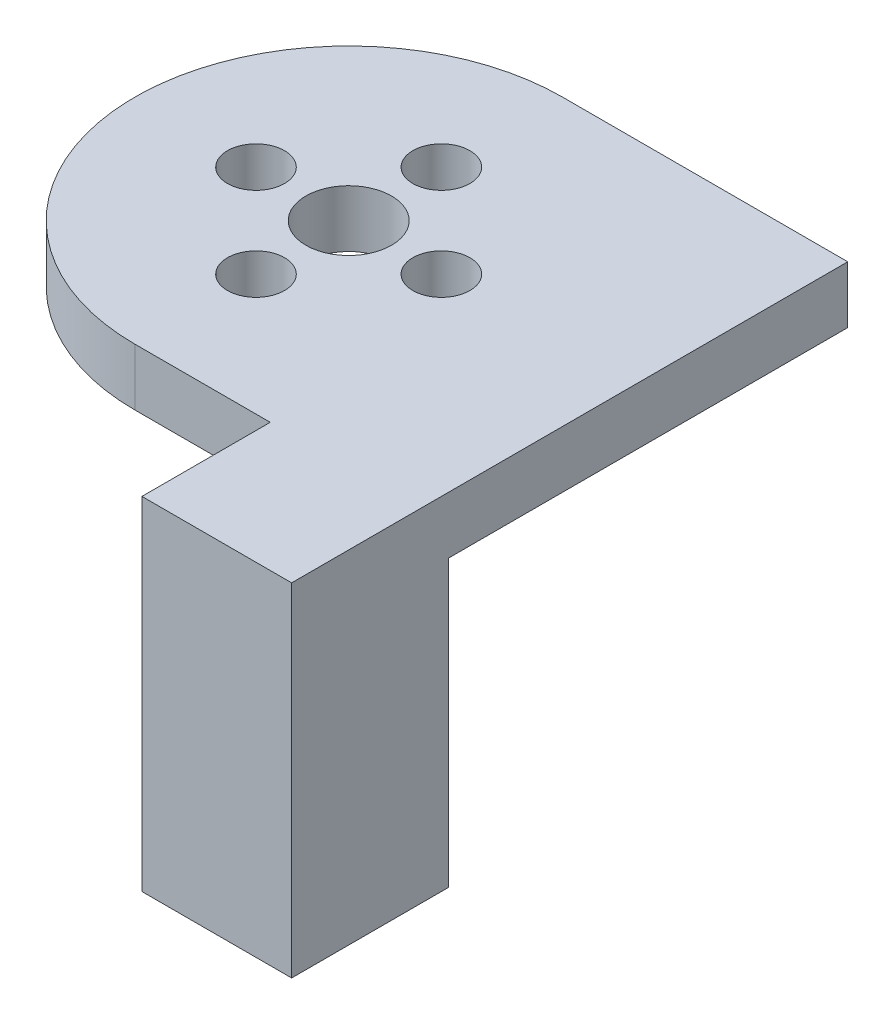
SolidWorks part; units mm, degrees
ref_plane "Front Plane" through (0, 0, 0) normal (0, 0, 1) x (1, 0, 0)
ref_plane "Top Plane" through (0, 0, 0) normal (0, 1, 0) x (1, 0, 0)
ref_plane "Right Plane" through (0, 0, 0) normal (1, 0, 0) x (0, 0, -1)
sketch "Sketch1" plane through (0, 0, 0) normal (0, 1, 0) x (1, 0, 0)
  line L1 (10, -15) -> (-10, -15)
  line L2 (10, -15) -> (10, 15)
  line L3 (10, 15) -> (-10, 15)
  line L5 (10, -15) -> (-10, 15) construction
  line L6 (10, 15) -> (-10, -15) construction
  arc A0 (-10, 15) -> (-10, -15) centre (-10, 0) ccw
  circle A1 centre (-10, 0) radius 3
  circle A2 centre (-10, 6.5) radius 2
  circle A3 centre (-3.5, 0) radius 2
  circle A4 centre (-10, -6.5) radius 2
  circle A5 centre (-16.5, 0) radius 2
  point P0 (0, 0)
  point P18 (-10, 0)
  dimension "D3" = 15
  dimension "D4" = 6
  dimension "D5" = 6.5
  dimension "D1" = 20
  dimension "D2" = 30
  dimension "D6" = 4
extrude "Boss-Extrude1" add sketch "Sketch1" along normal blind 4
sketch "Sketch5" plane through (0, 0, 15) normal (0, 0, 1) x (1, 0, 0)
  line L0 (-10, 4) -> (10, 4) construction
  line L1 (10, 0) -> (-0.5, 0)
  line L2 (10, 0) -> (10, 4)
  line L3 (10, 4) -> (-0.5, 4)
  line L4 (-0.5, 0) -> (-0.5, 4)
  dimension "D1" = 10.5
extrude "Boss-Extrude3" add sketch "Sketch5" along normal blind 9
sketch "Sketch6" plane through (0, 0, 0) normal (0, -1, 0) x (-1, 0, 0)
  line L0 (-10, -24) -> (-10, 15) construction
  line L1 (0.5, -24) -> (-10, -24)
  line L2 (0.5, -24) -> (0.5, -21)
  line L3 (0.5, -21) -> (-10, -21)
  line L4 (-10, -24) -> (-10, -21)
  dimension "D1" = 3
extrude "Boss-Extrude4" add sketch "Sketch6" along normal blind 20
sketch "Sketch7" plane through (0, 0, 0) normal (0, -1, 0) x (-1, 0, 0)
  line L0 (-6.7, -21) -> (-10, -21)
  line L1 (-10, -21) -> (-10, 15) construction
  line L2 (-6.7, -21) -> (-7, -13)
  line L3 (0.5, -21) -> (-10, -21) construction
  line L4 (-10, -21) -> (-10, -13)
  line L5 (-7, -13) -> (-10, -13)
  line L10 (-10, -21) -> (0.5, -21)
  line L11 (0.5, -21) -> (0.5, -15)
  line L12 (0.5, -15) -> (10, -15)
  line L13 (10, 15) -> (-10, 15)
  line L14 (-10, 15) -> (-10, -21)
  line L17 (0.5, -15) -> (10, -15)
  line L18 (10, 15) -> (-10, 15)
  line L19 (-10, 15) -> (-10, -21)
  arc A1 (10, -15) -> (10, 15) centre (10, 0) ccw
  arc A2 (10, -15) -> (10, 15) centre (10, 0) ccw
  line M6 (-10, -21) -> (0.5, -21)
  line M11 (-10, 15) -> (-10, -21)
  dimension "D1" = 3
  dimension "D2" = 0
  dimension "D3" = 3.3
  dimension "D4" = 8
extrude "Boss-Extrude5" add sketch "Sketch7" along normal blind 20 contours L2 L5 M11 M6 region at (8.4238, 0, 17.0635)
sketch "Sketch8" plane through (0, 0, 0) normal (0, -1, 0) x (1, 0, 0)
  line L0 (-0.5, 21) -> (-0.5, 13)
  dimension "D1" = 8
